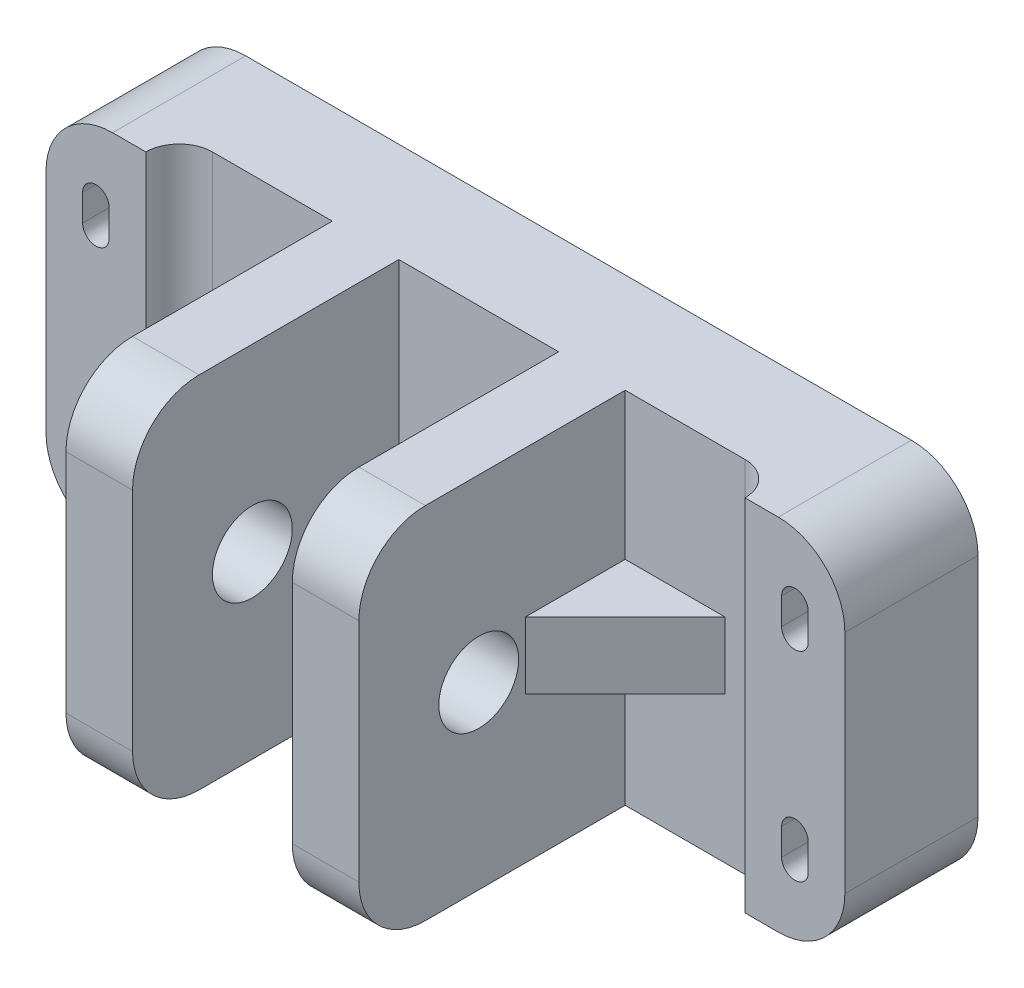
SolidWorks part; units mm, degrees
ref_plane "Płaszczyzna przednia" through (0, 0, 0) normal (0, 0, 1) x (1, 0, 0)
ref_plane "Płaszczyzna górna" through (0, 0, 0) normal (0, 1, 0) x (1, 0, 0)
ref_plane "Płaszczyzna prawa" through (0, 0, 0) normal (1, 0, 0) x (0, 0, -1)
sketch "Sketch1" plane through (0, 0, 0) normal (0, 0, 1) x (1, 0, 0)
  line L0 (-52.5, 17) -> (-52.5, 13) construction
  line L1 (-50, -27) -> (50, -27)
  line L2 (-60, -17) -> (-60, 17)
  line L3 (-50, 27) -> (50, 27)
  line L4 (60, -17) -> (60, 17)
  line L5 (-60, -27) -> (60, 27) construction
  line L6 (-60, 27) -> (60, -27) construction
  line L7 (-45, 27) -> (-45, -27)
  line L8 (-50.5, 17) -> (-50.5, 13)
  line L9 (-54.5, 17) -> (-54.5, 13)
  line L12 (52.5, -17) -> (52.5, -13) construction
  line L13 (50.5, -17) -> (50.5, -13)
  line L14 (54.5, -17) -> (54.5, -13)
  line L15 (45, 27) -> (45, -27)
  line L18 (0, 27) -> (0, -27) construction
  line L19 (-60, 0) -> (60, 0) construction
  line L20 (-52.5, -17) -> (-52.5, -13) construction
  line L21 (-50.5, -17) -> (-50.5, -13)
  line L22 (-54.5, -17) -> (-54.5, -13)
  line L23 (52.5, 17) -> (52.5, 13) construction
  line L24 (50.5, 17) -> (50.5, 13)
  line L25 (54.5, 17) -> (54.5, 13)
  line L152 (-17, -52.5) -> (-13, -52.5) construction
  line L153 (-17, -50.5) -> (-13, -50.5)
  line L154 (-17, -54.5) -> (-13, -54.5)
  line L155 (17, 52.5) -> (13, 52.5) construction
  line L156 (17, 50.5) -> (13, 50.5)
  line L157 (17, 54.5) -> (13, 54.5)
  line L158 (-17, -52.5) -> (-13, -52.5) construction
  line L159 (-17, -50.5) -> (-13, -50.5)
  line L160 (-17, -54.5) -> (-13, -54.5)
  line L161 (17, 52.5) -> (13, 52.5) construction
  line L162 (17, 50.5) -> (13, 50.5)
  line L163 (17, 54.5) -> (13, 54.5)
  arc A0 (-50.5, 17) -> (-54.5, 17) centre (-52.5, 17) ccw
  arc A1 (-54.5, 13) -> (-50.5, 13) centre (-52.5, 13) ccw
  arc A4 (50.5, -17) -> (54.5, -17) centre (52.5, -17) ccw
  arc A5 (54.5, -13) -> (50.5, -13) centre (52.5, -13) ccw
  arc A8 (-50.5, -17) -> (-54.5, -17) centre (-52.5, -17) cw
  arc A9 (-54.5, -13) -> (-50.5, -13) centre (-52.5, -13) cw
  arc A10 (50.5, 17) -> (54.5, 17) centre (52.5, 17) cw
  arc A11 (54.5, 13) -> (50.5, 13) centre (52.5, 13) cw
  arc A16 (-50, -27) -> (-60, -17) centre (-50, -17) cw
  arc A17 (50, -27) -> (60, -17) centre (50, -17) ccw
  arc A18 (50, 27) -> (60, 17) centre (50, 17) cw
  arc A19 (-60, 17) -> (-50, 27) centre (-50, 17) cw
  arc A104 (-17, -50.5) -> (-17, -54.5) centre (-17, -52.5) ccw
  arc A105 (-13, -54.5) -> (-13, -50.5) centre (-13, -52.5) ccw
  arc A106 (17, 50.5) -> (17, 54.5) centre (17, 52.5) ccw
  arc A107 (13, 54.5) -> (13, 50.5) centre (13, 52.5) ccw
  point P0 (0, 0)
  point P10 (-52.5, 15)
  point P19 (-15, -52.5)
  point P26 (52.5, -15)
  point P38 (0, 0)
  point P42 (-52.5, -15)
  point P49 (52.5, 15)
  point P58 (15, 52.5)
  point P72 (-15, -52.5)
  point P79 (15, 52.5)
  point P86 (-15, -52.5)
  point P93 (15, 52.5)
  point P100 (-15, -52.5)
  point P107 (15, 52.5)
  point P114 (-15, -52.5)
  point P121 (15, 52.5)
  point P128 (-15, -52.5)
  point P135 (15, 52.5)
  point P142 (-15, -52.5)
  point P149 (15, 52.5)
  point P156 (-15, -52.5)
  point P163 (15, 52.5)
  point P170 (-15, -52.5)
  point P177 (15, 52.5)
  point P184 (-15, -52.5)
  point P191 (15, 52.5)
  point P198 (-15, -52.5)
  point P205 (15, 52.5)
  point P212 (-15, -52.5)
  point P219 (15, 52.5)
  point P226 (-15, -52.5)
  point P233 (15, 52.5)
  point P240 (-15, -52.5)
  point P247 (15, 52.5)
  point P254 (-15, -52.5)
  point P261 (15, 52.5)
  point P268 (-15, -52.5)
  point P275 (15, 52.5)
  point P282 (-15, -52.5)
  point P289 (15, 52.5)
  point P296 (-15, -52.5)
  point P303 (15, 52.5)
  point P310 (-15, -52.5)
  point P317 (15, 52.5)
  point P324 (-15, -52.5)
  point P331 (15, 52.5)
  point P338 (-15, -52.5)
  point P345 (15, 52.5)
  point P352 (-15, -52.5)
  point P359 (15, 52.5)
  point P366 (-15, -52.5)
  point P373 (15, 52.5)
  dimension "D3" = 2
  dimension "D5" = 105
  dimension "D8" = 10
  dimension "D1" = 120
  dimension "D2" = 54
  dimension "D6" = 30
  dimension "D7" = 4
  dimension "D9" = 15
  dimension "D4" = 4
extrude "Boss-Extrude3" add sketch "Sketch1" along normal blind 20 contours A19 L2 A16 L1 L7 L3 L22 A9 L21 A8 A1 L9 A0 L8 | A18 L3 L15 L1 A17 L4 A5 L14 A4 L13 L25 A11 L24 A10 region at (-52.1816, 0, 0) region at (52.1816, 0, 0)
extrude "Boss-Extrude4" add sketch "Sketch1<10>" along normal blind 15 contours L15 L3 L7 L1 region at (0, 0, 0)
sketch "Sketch1<10>" plane through (0, 0, 0) normal (0, 0, 1) x (1, 0, 0) same geometry as "Sketch1"
fillet "Fillet1" radius 5 2 edges at (45, 0, 15) (-45, 0, 15)
sketch "Sketch7" plane through (0, 0, 0) normal (1, 0, 0) x (0, 0, -1)
  line L1 (-15, 27) -> (-45, 27)
  line L2 (-15, 27) -> (-15, -27)
  line L3 (-15, -27) -> (-45, -27)
  line L4 (-55, 17) -> (-55, -17)
  arc A0 (-45, -27) -> (-55, -17) centre (-45, -17) cw
  arc A1 (-45, 27) -> (-55, 17) centre (-45, 17) ccw
  circle A2 centre (-37, 0) radius 6
  point P10 (-55, 27)
  dimension "D2" = 10
  dimension "D3" = 12
  dimension "D1" = 40
  dimension "D4" = 37
extrude "Boss-Extrude5" add sketch "Sketch7" along normal mid plane 44
sketch "Sketch8" plane through (0, -27, 0) normal (0, -1, 0) x (1, 0, 0)
  line L0 (22, 55) -> (-22, 55) construction
  line L1 (12, 15) -> (-12, 15)
  line L2 (12, 15) -> (12, 55)
  line L3 (12, 55) -> (-12, 55)
  line L4 (-12, 15) -> (-12, 55)
  line L5 (-22, 45) -> (-22, 15) construction
  dimension "D1" = 24
  dimension "D2" = 10
extrude "Cut-Extrude1" cut sketch "Sketch8" against normal through all
sketch "Sketch9" plane through (0, -27, 0) normal (0, -1, 0) x (1, 0, 0)
  line L0 (-22, 15) -> (-37, 15)
  line L1 (-40, 15) -> (-22, 15) construction
  line L3 (-22, 45) -> (-22, 15) construction
  line L4 (-22, 30) -> (-37, 15)
  line L5 (-22, 30) -> (-22, 15)
  dimension "D1" = 15
  dimension "D2" = 15
extrude "Boss-Extrude6" add sketch "Sketch9" against normal blind 10 from offset 22 offset against normal yes
sketch "Sketch10" plane through (0, -27, 0) normal (0, -1, 0) x (1, 0, 0)
  line L0 (0, 0) -> (0, 55.3027) construction
  line L1 (22, 15) -> (37, 15)
  line L2 (22, 15) -> (40, 15) construction
  line L3 (22, 15) -> (22, 30)
  line L5 (22, 45) -> (22, 15) construction
  line L6 (22, 30) -> (37, 15)
  dimension "D2" = 15
  dimension "D1" = 15
extrude "Boss-Extrude7" add sketch "Sketch10" against normal blind 10 from offset 22 offset against normal yes
